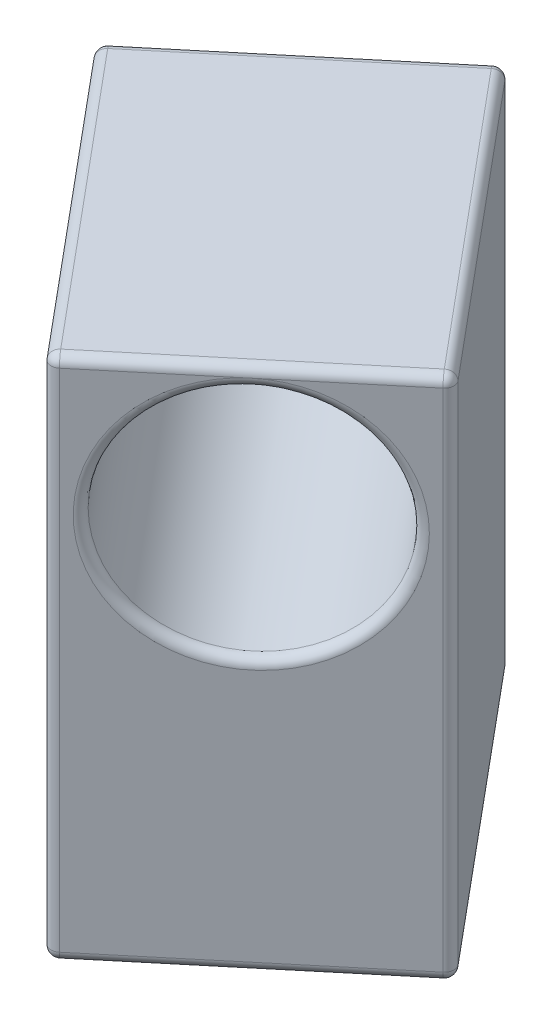
SolidWorks part; units mm, degrees
ref_plane "Front Plane" through (0, 0, 0) normal (0, 0, 1) x (1, 0, 0)
ref_plane "Top Plane" through (0, 0, 0) normal (0, 1, 0) x (1, 0, 0)
ref_plane "Right Plane" through (0, 0, 0) normal (1, 0, 0) x (0, 0, -1)
sketch "Sketch1" plane through (0, 0, 0) normal (0, 1, 0) x (1, 0, 0)
  line L0 (0, 0) -> (640, 0) construction
  line L1 (0, 0) -> (591.2829, 244.9174)
  line L2 (0, 0) -> (591.2829, -244.9174)
  line L3 (0, 0) -> (244.9174, -591.2829)
  line L4 (0, 0) -> (-244.9174, -591.2829)
  line L5 (0, 0) -> (-591.2829, -244.9174)
  line L6 (0, 0) -> (-591.2829, 244.9174)
  line L7 (0, 0) -> (-244.9174, 591.2829)
  line L8 (0, 0) -> (244.9174, 591.2829)
  line L9 (0, 145) -> (55, 145) construction
  line L10 (0, 0) -> (100, 0) construction
  line L11 (0, 0) -> (0, 145) construction
  line L14 (100, 0) -> (100, 145) construction
  circle A0 centre (0, 0) radius 640 construction
  point P15 (0, 0)
  dimension "D1" = 1280
  dimension "D2" = 22.5
  dimension "D4" = 145
  dimension "D5" = 100
  dimension "D6" = 55
  dimension "D3" = 8
sketch "Sketch2" plane through (0, 0, 0) normal (0, 1, 0) x (1, 0, 0)
  line L0 (-486.9956, 169.5033) -> (-66.9956, 169.5033) construction
  line L1 (-188.7141, -86.1278) -> (-188.7141, 241.8722) construction
  line L2 (525.6625, -1048.8053) -> (466.9027, -726.1115) construction
sketch "Sketch3" plane through (0, 0, 0) normal (0, 1, 0) x (1, 0, 0)
  line L0 (0, 0) -> (381.2468, 0) construction
  line L5 (0, 0) -> (0, 199.4415) construction
  line L6 (-10.2736, 158.9263) -> (10.2736, 158.9263)
  line L7 (10.2736, 158.9263) -> (13.1995, 163.9003)
  line L8 (13.1995, 163.9003) -> (45.5131, 148.2994)
  line L9 (45.5131, 148.2994) -> (66.2904, 80.9335)
  line L10 (66.2904, 80.9335) -> (73.8622, 80.9335)
  line L11 (73.8622, 80.9335) -> (86.8684, 42.4396)
  line L12 (86.8684, 42.4396) -> (86.8684, 30.0712)
  line L13 (86.8684, 30.0712) -> (81.3965, 24.5993)
  line L14 (81.3965, 24.5993) -> (81.3965, -24.5993)
  line L15 (-5.8349, 67.4929) -> (5.8349, 67.4929) construction
  line L16 (16.6008, 64.1674) -> (16.6008, 27.6557) construction
  line L17 (16.6008, 27.6557) -> (13.2646, 22.809) construction
  line L18 (13.2646, 22.809) -> (13.2646, -22.809) construction
  line L19 (5.8349, 128.0146) -> (5.8349, 107.4452)
  line L22 (5.8349, 107.4452) -> (9.2702, 107.4452)
  line L25 (9.2702, 107.4452) -> (10.663, 103.7163)
  line L26 (10.663, 103.7163) -> (20.7578, 101.0699)
  line L27 (20.7578, 101.0699) -> (32.199, 111.7601)
  line L28 (32.199, 111.7601) -> (32.199, 123.5038)
  line L29 (32.199, 123.5038) -> (24.9078, 123.5038)
  line L30 (24.9078, 123.5038) -> (13.8412, 132.5856)
  line L31 (13.8412, 132.5856) -> (9.2702, 132.5856)
  line L32 (9.2702, 132.5856) -> (5.8349, 128.0146)
  line L33 (41.9414, 39.7891) -> (51.4866, 54.1602)
  line L34 (51.4866, 54.1602) -> (55.4027, 54.1602)
  line L35 (55.4027, 54.1602) -> (58.1637, 51.3993)
  line L36 (58.1637, 51.3993) -> (58.1637, 43.1872)
  line L37 (58.1637, 43.1872) -> (66.3555, 28.462)
  line L38 (66.3555, 28.462) -> (66.3555, 24.0728)
  line L39 (66.3555, 24.0728) -> (62.2596, 17.9061)
  line L40 (62.2596, 17.9061) -> (47.8497, 18.1669)
  line L41 (47.8497, 18.1669) -> (41.9414, 27.1878)
  line L42 (41.9414, 27.1878) -> (41.9414, 39.7891)
  line L43 (-41.9414, 27.1878) -> (-41.9414, 39.7891)
  line L44 (-47.8497, 18.1669) -> (-41.9414, 27.1878)
  line L45 (-62.2596, 17.9061) -> (-47.8497, 18.1669)
  line L46 (-66.3555, 24.0728) -> (-62.2596, 17.9061)
  line L47 (-66.3555, 28.462) -> (-66.3555, 24.0728)
  line L48 (-58.1637, 43.1872) -> (-66.3555, 28.462)
  line L49 (-58.1637, 51.3993) -> (-58.1637, 43.1872)
  line L50 (-55.4027, 54.1602) -> (-58.1637, 51.3993)
  line L51 (-51.4866, 54.1602) -> (-55.4027, 54.1602)
  line L52 (-41.9414, 39.7891) -> (-51.4866, 54.1602)
  line L53 (-9.2702, 132.5856) -> (-5.8349, 128.0146)
  line L54 (-13.8412, 132.5856) -> (-9.2702, 132.5856)
  line L55 (-24.9078, 123.5038) -> (-13.8412, 132.5856)
  line L56 (-32.199, 123.5038) -> (-24.9078, 123.5038)
  line L57 (-32.199, 111.7601) -> (-32.199, 123.5038)
  line L58 (-20.7578, 101.0699) -> (-32.199, 111.7601)
  line L59 (-10.663, 103.7163) -> (-20.7578, 101.0699)
  line L60 (-9.2702, 107.4452) -> (-10.663, 103.7163)
  line L61 (-5.8349, 107.4452) -> (-9.2702, 107.4452)
  line L62 (-5.8349, 128.0146) -> (-5.8349, 107.4452)
  line L63 (-13.2646, 22.809) -> (-13.2646, -22.809) construction
  line L64 (-16.6008, 27.6557) -> (-13.2646, 22.809) construction
  line L65 (-16.6008, 64.1674) -> (-16.6008, 27.6557) construction
  line L66 (-81.3965, 24.5993) -> (-81.3965, -24.5993)
  line L67 (-86.8684, 30.0712) -> (-81.3965, 24.5993)
  line L68 (-86.8684, 42.4396) -> (-86.8684, 30.0712)
  line L69 (-73.8622, 80.9335) -> (-86.8684, 42.4396)
  line L70 (-66.2904, 80.9335) -> (-73.8622, 80.9335)
  line L71 (-45.5131, 148.2994) -> (-66.2904, 80.9335)
  line L72 (-13.1995, 163.9003) -> (-45.5131, 148.2994)
  line L73 (-10.2736, 158.9263) -> (-13.1995, 163.9003)
  line L74 (-10.2736, -158.9263) -> (-13.1995, -163.9003)
  line L75 (-13.1995, -163.9003) -> (-45.5131, -148.2994)
  line L76 (-45.5131, -148.2994) -> (-66.2904, -80.9335)
  line L77 (-66.2904, -80.9335) -> (-73.8622, -80.9335)
  line L78 (-73.8622, -80.9335) -> (-86.8684, -42.4396)
  line L79 (-86.8684, -42.4396) -> (-86.8684, -30.0712)
  line L80 (-86.8684, -30.0712) -> (-81.3965, -24.5993)
  line L81 (-16.6008, -64.1674) -> (-16.6008, -27.6557) construction
  line L82 (-16.6008, -27.6557) -> (-13.2646, -22.809) construction
  line L83 (-5.8349, -128.0146) -> (-5.8349, -107.4452)
  line L84 (-5.8349, -107.4452) -> (-9.2702, -107.4452)
  line L85 (-9.2702, -107.4452) -> (-10.663, -103.7163)
  line L86 (-10.663, -103.7163) -> (-20.7578, -101.0699)
  line L87 (-20.7578, -101.0699) -> (-32.199, -111.7601)
  line L88 (-32.199, -111.7601) -> (-32.199, -123.5038)
  line L89 (-32.199, -123.5038) -> (-24.9078, -123.5038)
  line L90 (-24.9078, -123.5038) -> (-13.8412, -132.5856)
  line L91 (-13.8412, -132.5856) -> (-9.2702, -132.5856)
  line L92 (-9.2702, -132.5856) -> (-5.8349, -128.0146)
  line L93 (-41.9414, -39.7891) -> (-51.4866, -54.1602)
  line L94 (-51.4866, -54.1602) -> (-55.4027, -54.1602)
  line L95 (-55.4027, -54.1602) -> (-58.1637, -51.3993)
  line L96 (-58.1637, -51.3993) -> (-58.1637, -43.1872)
  line L97 (-58.1637, -43.1872) -> (-66.3555, -28.462)
  line L98 (-66.3555, -28.462) -> (-66.3555, -24.0728)
  line L99 (-66.3555, -24.0728) -> (-62.2596, -17.9061)
  line L100 (-62.2596, -17.9061) -> (-47.8497, -18.1669)
  line L101 (-47.8497, -18.1669) -> (-41.9414, -27.1878)
  line L102 (-41.9414, -27.1878) -> (-41.9414, -39.7891)
  line L103 (41.9414, -27.1878) -> (41.9414, -39.7891)
  line L104 (47.8497, -18.1669) -> (41.9414, -27.1878)
  line L105 (62.2596, -17.9061) -> (47.8497, -18.1669)
  line L106 (66.3555, -24.0728) -> (62.2596, -17.9061)
  line L107 (66.3555, -28.462) -> (66.3555, -24.0728)
  line L108 (58.1637, -43.1872) -> (66.3555, -28.462)
  line L109 (58.1637, -51.3993) -> (58.1637, -43.1872)
  line L110 (55.4027, -54.1602) -> (58.1637, -51.3993)
  line L111 (51.4866, -54.1602) -> (55.4027, -54.1602)
  line L112 (41.9414, -39.7891) -> (51.4866, -54.1602)
  line L113 (9.2702, -132.5856) -> (5.8349, -128.0146)
  line L114 (13.8412, -132.5856) -> (9.2702, -132.5856)
  line L115 (24.9078, -123.5038) -> (13.8412, -132.5856)
  line L116 (32.199, -123.5038) -> (24.9078, -123.5038)
  line L117 (32.199, -111.7601) -> (32.199, -123.5038)
  line L118 (20.7578, -101.0699) -> (32.199, -111.7601)
  line L119 (10.663, -103.7163) -> (20.7578, -101.0699)
  line L120 (9.2702, -107.4452) -> (10.663, -103.7163)
  line L121 (5.8349, -107.4452) -> (9.2702, -107.4452)
  line L122 (5.8349, -128.0146) -> (5.8349, -107.4452)
  line L123 (16.6008, -27.6557) -> (13.2646, -22.809) construction
  line L124 (16.6008, -64.1674) -> (16.6008, -27.6557) construction
  line L125 (-5.8349, -67.4929) -> (5.8349, -67.4929) construction
  line L126 (86.8684, -30.0712) -> (81.3965, -24.5993)
  line L127 (86.8684, -42.4396) -> (86.8684, -30.0712)
  line L128 (73.8622, -80.9335) -> (86.8684, -42.4396)
  line L129 (66.2904, -80.9335) -> (73.8622, -80.9335)
  line L130 (45.5131, -148.2994) -> (66.2904, -80.9335)
  line L131 (13.1995, -163.9003) -> (45.5131, -148.2994)
  line L132 (10.2736, -158.9263) -> (13.1995, -163.9003)
  line L133 (-10.2736, -158.9263) -> (10.2736, -158.9263)
  line L134 (-5.3457, 68.4929) -> (5.3457, 68.4929)
  line L135 (17.6008, 64.1674) -> (17.6008, 27.3448)
  line L136 (17.6008, 27.3448) -> (14.2646, 22.498)
  line L137 (14.2646, 22.498) -> (14.2646, -22.498)
  line L138 (-17.6008, 64.1674) -> (-17.6008, 27.3448)
  line L139 (-17.6008, 27.3448) -> (-14.2646, 22.498)
  line L140 (-5.3457, 68.4929) -> (5.3457, 68.4929) construction
  line L141 (14.2646, 22.498) -> (14.2646, -22.498) construction
  line L142 (17.6008, -27.3448) -> (14.2646, -22.498) construction
  line L143 (17.6008, -64.1674) -> (17.6008, -27.3448) construction
  line L144 (-14.2646, 22.498) -> (-14.2646, -22.498)
  line L145 (17.6008, -64.1674) -> (17.6008, -27.3448)
  line L146 (17.6008, -27.3448) -> (14.2646, -22.498)
  line L147 (-17.6008, -27.3448) -> (-14.2646, -22.498)
  line L148 (-17.6008, -64.1674) -> (-17.6008, -27.3448)
  line L149 (-5.3457, -68.4929) -> (5.3457, -68.4929)
  arc A0 (5.8349, 67.4929) -> (16.6008, 64.0252) centre (10.663, 64.0364) cw construction
  arc A5 (-5.8349, 67.4929) -> (-16.6008, 64.0252) centre (-10.663, 64.0364) ccw construction
  arc A6 (-5.8349, -67.4929) -> (-16.6008, -64.0252) centre (-10.663, -64.0364) cw construction
  arc A7 (5.8349, -67.4929) -> (16.6008, -64.0252) centre (10.663, -64.0364) ccw construction
  arc A8 (-5.3457, 68.4929) -> (-17.6008, 64.0234) centre (-10.663, 64.0364) ccw
  arc A9 (5.3457, 68.4929) -> (17.6008, 64.0234) centre (10.663, 64.0364) cw
  arc A10 (-5.3457, 68.4929) -> (-17.6008, 64.0234) centre (-10.663, 64.0364) ccw construction
  arc A11 (5.3457, -68.4929) -> (17.6008, -64.0234) centre (10.663, -64.0364) ccw
  arc A12 (-5.3457, -68.4929) -> (-17.6008, -64.0234) centre (-10.663, -64.0364) cw
  ellipse E0 centre (11.3851, 149.6854) end of major axis (12.0553, 155.2702) minor radius 3.0047
  ellipse E1 centre (33.6925, 82.363) end of major axis (41.1096, 88.3895) minor radius 4.3287
  ellipse E2 centre (44.8955, 74.0187) end of major axis (51.4866, 79.374) minor radius 4.6847
  ellipse E3 centre (66.3555, 66.447) end of major axis (67.1471, 72.2416) minor radius 3.5711
  ellipse E4 centre (-66.3555, 66.447) end of major axis (-67.1471, 72.2416) minor radius 3.5711
  ellipse E5 centre (-44.8955, 74.0187) end of major axis (-51.4866, 79.374) minor radius 4.6847
  ellipse E6 centre (-33.6925, 82.363) end of major axis (-41.1096, 88.3895) minor radius 4.3287
  ellipse E7 centre (-11.3851, 149.6854) end of major axis (-12.0553, 155.2702) minor radius 3.0047
  ellipse E8 centre (-11.3851, -149.6854) end of major axis (-12.0553, -155.2702) minor radius 3.0047
  ellipse E9 centre (-33.6925, -82.363) end of major axis (-41.1096, -88.3895) minor radius 4.3287
  ellipse E10 centre (-44.8955, -74.0187) end of major axis (-51.4866, -79.374) minor radius 4.6847
  ellipse E11 centre (-66.3555, -66.447) end of major axis (-67.1471, -72.2416) minor radius 3.5711
  ellipse E12 centre (66.3555, -66.447) end of major axis (67.1471, -72.2416) minor radius 3.5711
  ellipse E13 centre (44.8955, -74.0187) end of major axis (51.4866, -79.374) minor radius 4.6847
  ellipse E14 centre (33.6925, -82.363) end of major axis (41.1096, -88.3895) minor radius 4.3287
  ellipse E15 centre (11.3851, -149.6854) end of major axis (12.0553, -155.2702) minor radius 3.0047
  point P117 (0, 67.4929)
  point P126 (0, 158.9263)
  point P180 (0, -158.9263)
  point P181 (0, -67.4929)
  point P190 (-81.3965, 0)
  point P193 (-13.2646, 0)
  point P234 (13.2646, 0)
  point P237 (81.3965, 0)
  point P261 (0, 68.4929)
  point P271 (14.2646, 0)
  point P274 (-14.2646, 0)
  dimension "D1" = 1
sketch "Sketch4" plane through (0, 0, 0) normal (0, 1, 0) x (1, 0, 0)
  line L0 (0, 0) -> (81.2255, 0) construction
  line L1 (0, 0) -> (0, 97.3086) construction
  line L2 (0, 0) -> (0, 199.4415) construction
  line L3 (-10.1399, 86.6928) -> (10.1399, 86.6928)
  line L4 (10.1399, 86.6928) -> (16.0235, 80.8091)
  line L5 (16.0235, 80.8091) -> (23.9736, 57.3032)
  line L6 (23.9736, 57.3032) -> (23.9736, 47.8894)
  line L7 (23.9736, 47.8894) -> (21.6776, 47.8894)
  line L8 (21.6776, 47.8894) -> (21.6776, 27.2256)
  line L9 (21.6776, 27.2256) -> (27.5382, 22.1416)
  line L10 (27.5382, 22.1416) -> (27.5382, 14.9676)
  line L11 (27.5382, 14.9676) -> (23.9736, 10.8585)
  line L12 (23.9736, 10.8585) -> (23.9736, -10.8585)
  line L13 (-23.9736, 10.8585) -> (-23.9736, -10.8585)
  line L14 (-27.5382, 14.9676) -> (-23.9736, 10.8585)
  line L15 (-27.5382, 22.1416) -> (-27.5382, 14.9676)
  line L16 (-21.6776, 27.2256) -> (-27.5382, 22.1416)
  line L17 (-21.6776, 47.8894) -> (-21.6776, 27.2256)
  line L18 (-23.9736, 47.8894) -> (-21.6776, 47.8894)
  line L19 (-23.9736, 57.3032) -> (-23.9736, 47.8894)
  line L20 (-16.0235, 80.8091) -> (-23.9736, 57.3032)
  line L21 (-10.1399, 86.6928) -> (-16.0235, 80.8091)
  line L22 (-10.1399, -86.6928) -> (-16.0235, -80.8091)
  line L23 (-16.0235, -80.8091) -> (-23.9736, -57.3032)
  line L24 (-23.9736, -57.3032) -> (-23.9736, -47.8894)
  line L25 (-23.9736, -47.8894) -> (-21.6776, -47.8894)
  line L26 (-21.6776, -47.8894) -> (-21.6776, -27.2256)
  line L27 (-21.6776, -27.2256) -> (-27.5382, -22.1416)
  line L28 (-27.5382, -22.1416) -> (-27.5382, -14.9676)
  line L29 (-27.5382, -14.9676) -> (-23.9736, -10.8585)
  line L30 (27.5382, -14.9676) -> (23.9736, -10.8585)
  line L31 (27.5382, -22.1416) -> (27.5382, -14.9676)
  line L32 (21.6776, -27.2256) -> (27.5382, -22.1416)
  line L33 (21.6776, -47.8894) -> (21.6776, -27.2256)
  line L34 (23.9736, -47.8894) -> (21.6776, -47.8894)
  line L35 (23.9736, -57.3032) -> (23.9736, -47.8894)
  line L36 (16.0235, -80.8091) -> (23.9736, -57.3032)
  line L37 (10.1399, -86.6928) -> (16.0235, -80.8091)
  line L38 (-10.1399, -86.6928) -> (10.1399, -86.6928)
  point P3 (0, -86.6928)
  point P27 (0, 86.6928)
  point P37 (-23.9736, 0)
  point P38 (23.9736, 0)
sketch "Sketch5" plane through (0, 0, 0) normal (0, 1, 0) x (1, 0, 0)
  line L0 (0, 68.4929) -> (0, 86.6928) construction
  line L1 (15.4511, 110) -> (223.3697, 546.0887)
  line L2 (0, 0) -> (0, 251.8084) construction
  line L3 (0, 110) -> (47.9221, 110) construction
  line L5 (244.9174, 616.9519) -> (262.4572, 609.0616) construction
  line L6 (262.4572, 609.0616) -> (269.1565, 599.6825) construction
  line L7 (269.1565, 599.6825) -> (256.4381, 571.4103) construction
  line L8 (256.4381, 571.4103) -> (244.9174, 563.1812) construction
  line L9 (244.9174, 563.1812) -> (221.08, 517.0826) construction
  line L10 (221.08, 517.0826) -> (201.6817, 527.1134) construction
  line L11 (201.6817, 527.1134) -> (221.6088, 571.4103) construction
  line L12 (221.6088, 571.4103) -> (218.2415, 584.6462) construction
  line L13 (218.2415, 584.6462) -> (232.4366, 616.2011) construction
  line L14 (232.4366, 616.2011) -> (244.9174, 616.9519) construction
  line L15 (244.9174, 591.2829) -> (309.3694, 564.586) construction
  line L16 (269.6266, 526.9284) -> (173.6132, 566.6985) construction
  line L18 (0, 0) -> (107.3069, 0) construction
  dimension "D1" = 110
  dimension "D2" = 50
sketch "Sketch6" plane through (0, 0, 0) normal (0, 1, 0) x (1, 0, 0)
  line L1 (27.9119, 24.7148) -> (544.6401, 226.6863)
  circle A0 centre (0, 0) radius 640 construction
  circle A1 centre (0, 0) radius 640 construction
  circle A3 centre (0, 0) radius 589.9318 construction
  dimension "D1" = 50.0682
sketch "Sketch19" plane through (0, 0, 0) normal (0, 1, 0) x (1, 0, 0)
  line L0 (128.4599, 309.2664) -> (271.805, 137.4916)
  line L5 (26.7343, 104.6204) -> (234.6528, 540.7091)
  line L6 (26.7343, 104.6204) -> (234.6528, 540.7091) construction
  line L7 (4.1679, 115.3796) -> (212.0865, 551.4683)
  line L8 (4.1679, 115.3796) -> (212.0865, 551.4683) construction
  line L9 (20.631, 43.3425) -> (537.3592, 245.3139)
  line L10 (32.4624, 13.0726) -> (549.1907, 215.044)
  line L11 (32.4624, 13.0726) -> (549.1907, 215.044) construction
  line L12 (23.3613, 36.3571) -> (540.0895, 238.3286)
  line L13 (23.3613, 36.3571) -> (540.0895, 238.3286) construction
  line L14 (20.631, 43.3425) -> (537.3592, 245.3139) construction
  line L15 (30.1192, 103.0065) -> (238.0378, 539.0952)
  line L16 (30.1192, 103.0065) -> (238.0378, 539.0952) construction
  line L22 (21.9961, 39.8498) -> (538.7244, 241.8213)
  line L23 (21.9961, 39.8498) -> (538.7244, 241.8213) construction
  line L24 (33.5042, 101.3926) -> (241.4227, 537.4813)
  line L25 (33.5042, 101.3926) -> (241.4227, 537.4813) construction
  dimension "D1" = 12.5
  dimension "D2" = 12.5
  dimension "D3" = 12.5
  dimension "D4" = 12.5
  dimension "D5" = 16.25
  dimension "D8" = 16.25
  dimension "D10" = 20
  dimension "D11" = 20
sketch "Sketch27" plane through (0, 0, 0) normal (0, 1, 0) x (1, 0, 0)
  line L0 (128.4599, 309.2664) -> (271.805, 137.4916) construction
  line L1 (128.4599, 309.2664) -> (271.805, 137.4916) construction
  line L2 (122.7015, 304.461) -> (266.0466, 132.6862) construction
  line L3 (134.2183, 314.0717) -> (277.5634, 142.2969) construction
  line L4 (199.4837, 235.8621) -> (187.967, 226.2515) construction
  line L5 (205.8908, 228.1843) -> (194.3741, 218.5736) construction
  line L6 (212.2979, 220.5065) -> (200.7812, 210.8958) construction
  line L7 (187.967, 226.2515) -> (199.4837, 235.8621)
  line L8 (187.967, 226.2515) -> (200.7812, 210.8958)
  line L9 (199.4837, 235.8621) -> (212.2979, 220.5065)
  line L10 (200.7812, 210.8958) -> (212.2979, 220.5065)
  dimension "D1" = 7.5
  dimension "D2" = 7.5
  dimension "D3" = 10
  dimension "D4" = 10
extrude "Boss-Extrude1" add sketch "Sketch27" along normal blind 7 and the other way blind 20
sketch "Sketch28" plane through (0, -20, 0) normal (0, -1, 0) x (1, 0, 0)
  line L0 (187.967, -226.2515) -> (212.2979, -220.5065) construction
  circle A0 centre (200.1324, -223.379) radius 6
  dimension "D1" = 12
extrude "Cut-Extrude1" cut sketch "Sketch28" against normal blind 10
sweep "Cut-Sweep1" cut path "Sketch19" circular profile diameter 12 parameters "D3"=12
fillet "Fillet1" radius 0.5 15 edges at (200.1324, -20, -229.379) (193.7253, -20, -231.0568) (189.1186, 0, -227.2125) (205.8908, -20, -228.1843) (199.4837, -6.5, -235.8621) (206.5396, -20, -215.7011) (212.2979, -6.5, -220.5065) (211.1462, 0, -219.5454) (194.3741, -20, -218.5736) (187.967, -6.5, -226.2515) (200.7812, -6.5, -210.8958) (206.5396, 7, -215.7011) (194.3741, 7, -218.5736) (193.7253, 7, -231.0568) (205.8908, 7, -228.1843)
